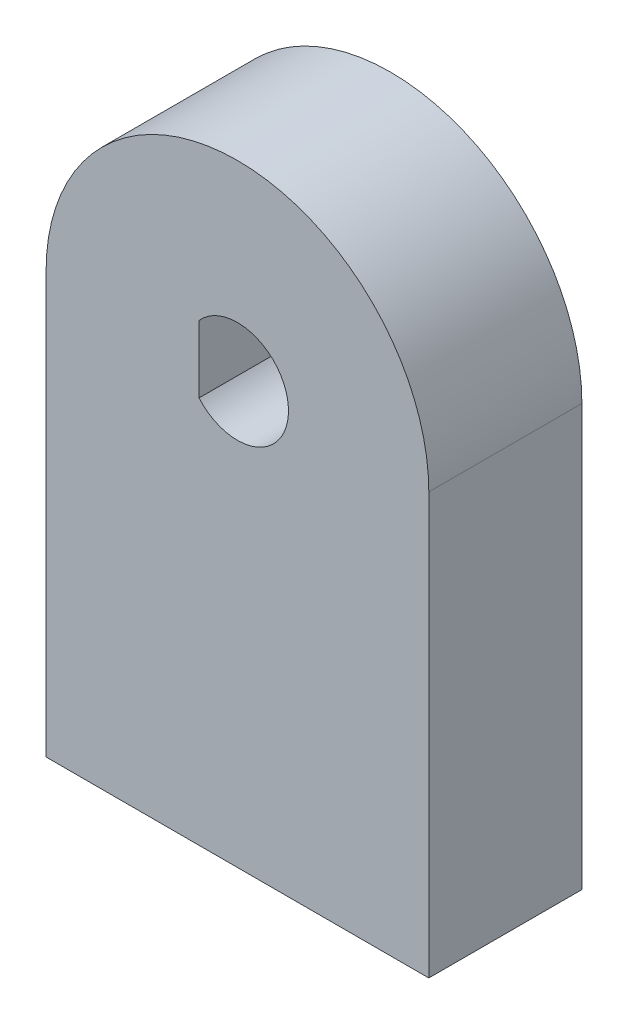
SolidWorks part; units mm, degrees
ref_plane "Front Plane" through (0, 0, 0) normal (0, 0, 1) x (1, 0, 0)
ref_plane "Top Plane" through (0, 0, 0) normal (0, 1, 0) x (1, 0, 0)
ref_plane "Right Plane" through (0, 0, 0) normal (1, 0, 0) x (0, 0, -1)
sketch "Sketch2" plane through (0, 0, 0) normal (0, 0, 1) x (1, 0, 0)
  circle A0 centre (0, 0) radius 15
  circle A1 centre (0, 0) radius 11
  dimension "D1" = 30
  dimension "D2" = 22
extrude "Boss-Extrude1" add sketch "Sketch2" along normal blind 4
sketch "Sketch3" plane through (0, 0, 4) normal (0, 0, 1) x (1, 0, 0)
  circle A0 centre (0, 0) radius 15
  circle A1 centre (0, 0) radius 4
  circle A2 centre (0, 0) radius 15 construction
  dimension "D1" = 8
  dimension "D2" = 0
extrude "Boss-Extrude2" add sketch "Sketch3" along normal blind 8
sketch "Sketch6" plane through (0, 0, 12) normal (0, 0, 1) x (1, 0, 0)
  line L0 (-15, 0) -> (-15, -33)
  line L1 (15, 0) -> (15, -33)
  line L2 (15, -33) -> (-15, -33)
  circle A0 centre (0, 0) radius 15 construction
  circle A2 centre (0, 0) radius 15
  arc A3 (-15, 0) -> (15, 0) centre (0, 0) ccw
  dimension "D1" = 33
  dimension "D2" = 0
extrude "Boss-Extrude5" add sketch "Sketch6" against normal blind 12
sketch "Sketch8" plane through (0, 0, 12) normal (0, 0, 1) x (1, 0, 0)
  line L0 (-3.0138, 2.63) -> (-3.0138, -2.63)
  arc A0 (-3.0138, 2.63) -> (-3.0138, -2.63) centre (0, 0) ccw
  dimension "D2" = 8
  dimension "D1" = 5.26
extrude "Boss-Extrude7" add sketch "Sketch8" against normal blind 8
